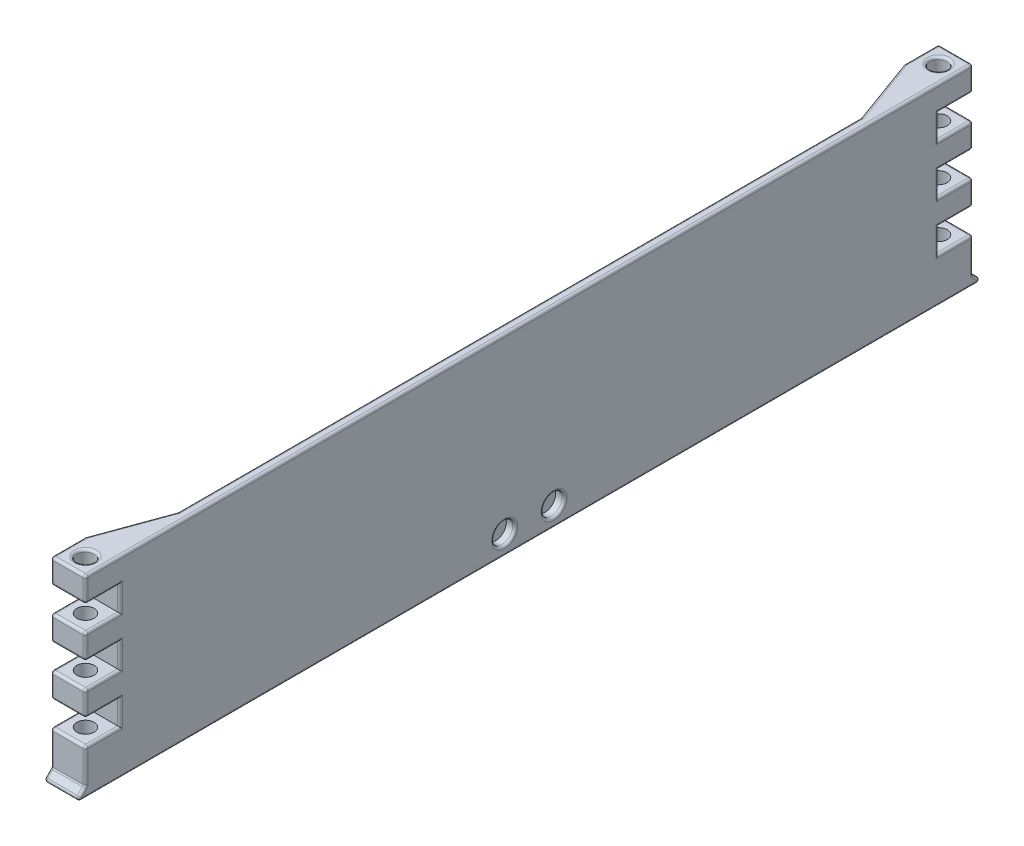
SolidWorks part; units mm, degrees
ref_plane "Front Plane" through (0, 0, 0) normal (0, 0, 1) x (1, 0, 0)
ref_plane "Top Plane" through (0, 0, 0) normal (0, 1, 0) x (1, 0, 0)
ref_plane "Right Plane" through (0, 0, 0) normal (1, 0, 0) x (0, 0, -1)
sketch "Sketch1" plane through (0, 0, 0) normal (1, 0, 0) x (0, 0, -1)
  line L1 (-45, -19.5) -> (45, -19.5)
  line L2 (-45, -5.5) -> (-45, -0.5)
  line L3 (-38, 19.5) -> (45, 19.5)
  line L4 (45, -19.5) -> (45, 19.5)
  line L5 (-45, -19.5) -> (45, 19.5) construction
  line L6 (-45, 19.5) -> (45, -19.5) construction
  line L8 (-47, -19.5) -> (-45, -19.5)
  line L12 (-38, 19.5) -> (-38, 14.5) construction
  line L13 (-38, 14.5) -> (-45, 14.5)
  line L14 (-38, 14.5) -> (-38, 9.5)
  line L15 (-38, 9.5) -> (-45, 9.5)
  line L16 (-38, 9.5) -> (-38, 4.5) construction
  line L17 (-38, 4.5) -> (-38, -0.5)
  line L18 (-38, -0.5) -> (-38, -5.5) construction
  line L19 (-38, -5.5) -> (-38, -10.5)
  line L20 (-38, 19.5) -> (-45, 19.5)
  line L21 (-45, 14.5) -> (-45, 19.5)
  line L22 (-38, -10.5) -> (-45, -10.5)
  line L23 (-38, -5.5) -> (-45, -5.5)
  line L24 (-38, -0.5) -> (-45, -0.5)
  line L25 (-38, 4.5) -> (-45, 4.5)
  line L26 (-45, 4.5) -> (-45, 9.5)
  line L43 (-45, -17.5) -> (-45, -10.5)
  line L44 (-45, -17.5) -> (-47, -19.5)
  line L45 (40, -19.5) -> (40, -15.5) construction
  line L46 (40, -15.5) -> (45, -15.5) construction
  circle A0 centre (40, -15.5) radius 2.15
  point P0 (0, 0)
  dimension "D9" = 4.3
  dimension "D1" = 39
  dimension "D2" = 90
  dimension "D3" = 2
  dimension "D4" = 7
  dimension "D5" = 5
  dimension "D6" = 2
  dimension "D7" = 4
  dimension "D8" = 5
extrude "Boss-Extrude1" add sketch "Sketch1" along normal blind 7 contours L13 L12 L3 L2 region at (0, -0.0067, -1.0863)
extrude "Boss-Extrude2" add sketch "Sketch1<3>" along normal blind 5.2 contours A0
sketch "Sketch1<3>" plane through (0, 0, 0) normal (1, 0, 0) x (0, 0, -1) same geometry as "Sketch1"
sketch "Sketch7" plane through (0, -19.5, 0) normal (0, -1, 0) x (1, 0, 0)
  line L1 (0, 47) -> (0, -45) construction
  line L2 (3.5, 41.5) -> (3.5, 45) construction
  line L3 (7, 45) -> (7, 38) construction
  line L4 (7, 38) -> (0, 38) construction
  line L5 (0, 38) -> (0, 45) construction
  line L6 (3.5, 45) -> (3.5, 47) construction
  line L7 (3.5, 45) -> (7, 45) construction
  line L8 (7, 38) -> (0, 45) construction
  line L9 (7, 47) -> (0, 47) construction
  line L10 (0.675, 39.869) -> (3.5, 38.238)
  line L11 (3.5, 38.238) -> (6.325, 39.869)
  line L12 (6.325, 39.869) -> (6.325, 43.131)
  line L13 (6.325, 43.131) -> (3.5, 44.762)
  line L14 (3.5, 44.762) -> (0.675, 43.131)
  line L15 (0.675, 43.131) -> (0.675, 39.869)
  line L16 (3.5, 38.238) -> (3.5, 38) construction
  circle A0 centre (3.5, 41.5) radius 1.75
  circle A1 centre (3.5, 41.5) radius 2.825 construction
  dimension "D4" = 5.65
  dimension "D5" = 3.5
  dimension "D1" = 2
  dimension "D2" = 7
  dimension "D3" = 7
extrude "Cut-Extrude3" cut sketch "Sketch7" against normal through all both and the other way through all contours A0 region at (3.5, -19.5, 41.5)
extrude "Cut-Extrude4" cut sketch "Sketch7<3>" against normal blind 6 and the other way through all contours L14 L15 L10 L11 L12 L13 A0 region at (0.7613, -19.5, 41.5)
sketch "Sketch7<3>" plane through (0, -19.5, 0) normal (0, -1, 0) x (1, 0, 0) same geometry as "Sketch7"
sketch "Sketch8" plane through (0, 19.5, 0) normal (0, 1, 0) x (1, 0, 0)
  line L0 (0, -38) -> (5, -24.2626)
  line L1 (0, -45) -> (0, 45) construction
  line L3 (7, 45) -> (0, 45) construction
  line L4 (0, -38) -> (0, 45)
  line L5 (0, 45) -> (5, 45) construction
  line L6 (5, -24.2626) -> (5, 45)
  line L9 (7, -45) -> (7, 45) construction
  line L10 (5, 45) -> (0, 45)
  point P12 (5, 44.8796)
  dimension "D2" = 7
  dimension "D3" = 2
  dimension "D4" = 200
extrude "Cut-Extrude5" cut sketch "Sketch8" against normal through all
mirror "Mirror2" about plane through (7, 0, -45) normal (0, 0, 1) of bodies 111 109
fillet "Fillet1" radius 0.5 84 edges at (2.5, -19.5, 31.1313) (2.5, -19.5, -121.1313) (0, -18.5, -136) (0, -18.5, 46) (3.5, -17.5, -135) (3.5, -10.5, -135) (0, -14, -135) (3.5, -5.5, -135) (3.5, -0.5, -135) (0, -3, -135) (3.5, 4.5, -135) (3.5, 9.5, -135) (0, 7, -135) (3.5, 14.5, -135) (0, 17, -135) (7, -10.5, 41.5) (7, -8, 38) (7, -5.5, 41.5) (7, -0.5, 41.5) (7, 2, 38) (7, 4.5, 41.5) (7, 9.5, 41.5) (7, 12, 38) (7, 14.5, 41.5) (7, 17, -135) (7, 14.5, -131.5) (7, 12, -128) (7, 9.5, -131.5) (7, 7, -135) (7, 4.5, -131.5) (7, 2, -128) (7, -0.5, -131.5) (7, -3, -135) (7, -5.5, -131.5) (7, -8, -128) (7, -10.5, -131.5) (7, -14, -135) (7, -18.5, -136) (7, -19.5, -45) (7, -18.5, 46) (3.5, -10.5, 45) (7, -14, 45) (3.5, -17.5, 45) (0, -14, 45) (3.5, -0.5, 45) (7, -3, 45) (3.5, -5.5, 45) (0, -3, 45) (3.5, 9.5, 45) (7, 7, 45) (3.5, 4.5, 45) (0, 7, 45) (7, 17, 45) (3.5, 14.5, 45) (0, 17, 45) (3.5, 19.5, -129.75) (3.5, 19.5, 39.75) (2.5, 19.5, -121.1313) (0, 19.5, -131.5) (3.5, 19.5, -135) (7, 19.5, -45) (3.5, 19.5, 45) (0, 19.5, 41.5) (2.5, 19.5, 31.1313) (0, -19.5, 42.5) (0, -19.5, -132.5) (0, 14.5, 41.5) (0, 9.5, 41.5) (0, 4.5, 41.5) (0, -0.5, 41.5) (0, -5.5, 41.5) (0, -10.5, 41.5) (0, -10.5, -131.5) (0, -5.5, -131.5) (0, -0.5, -131.5) (0, 4.5, -131.5) (0, 9.5, -131.5) (0, 14.5, -131.5) (3.5, -19.5, 47) (3.5, -19.5, -137) (7, -15.5, -47.85) (7, -15.5, -42.15) (5, 19.5, -45) (5, -19.5, -45)
